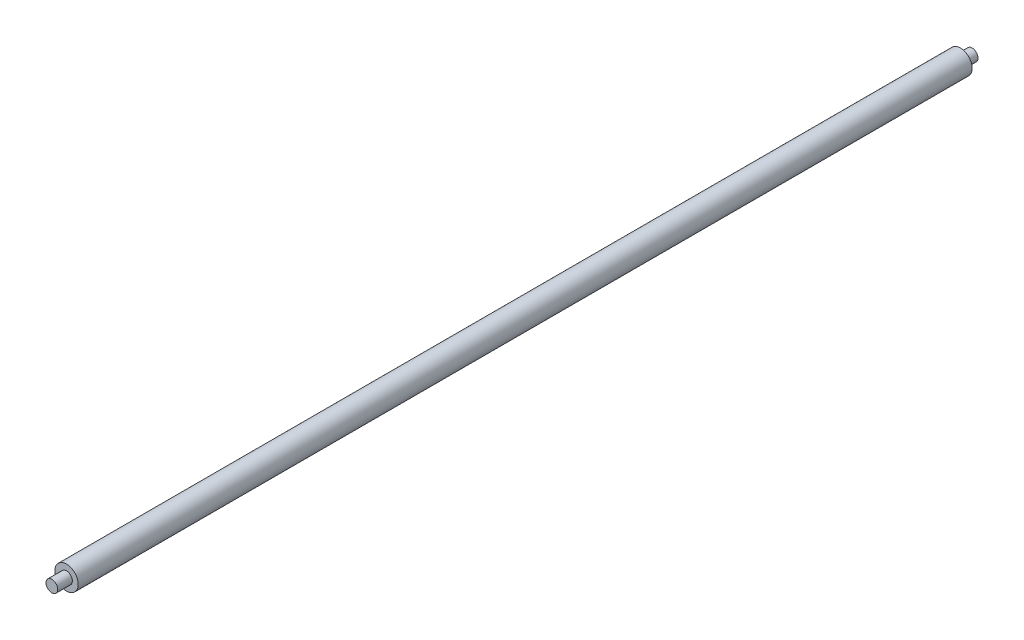
SolidWorks part; units mm, degrees
ref_plane "Front Plane" through (0, 0, 0) normal (0, 0, 1) x (1, 0, 0)
ref_plane "Top Plane" through (0, 0, 0) normal (0, 1, 0) x (1, 0, 0)
ref_plane "Right Plane" through (0, 0, 0) normal (1, 0, 0) x (0, 0, -1)
sketch "Sketch1" plane through (0, 0, 0) normal (0, 0, 1) x (1, 0, 0)
  circle A0 centre (0, 0) radius 6
  dimension "D1" = 12
extrude "Boss-Extrude1" add sketch "Sketch1" along normal mid plane 471
sketch "Sketch2" plane through (0, 0, 235.5) normal (0, 0, 1) x (1, 0, 0)
  circle A0 centre (0, 0) radius 6
  circle A1 centre (0, 0) radius 3
  dimension "D1" = 12
  dimension "D2" = 6
extrude "Cut-Extrude1" cut sketch "Sketch2" against normal blind 7.5
sketch "Sketch3" plane through (0, 0, -235.5) normal (0, 0, -1) x (-1, 0, 0)
  circle A0 centre (0, 0) radius 6
  circle A1 centre (0, 0) radius 3
  dimension "D1" = 6
  dimension "D2" = 12
extrude "Cut-Extrude2" cut sketch "Sketch3" against normal blind 6
